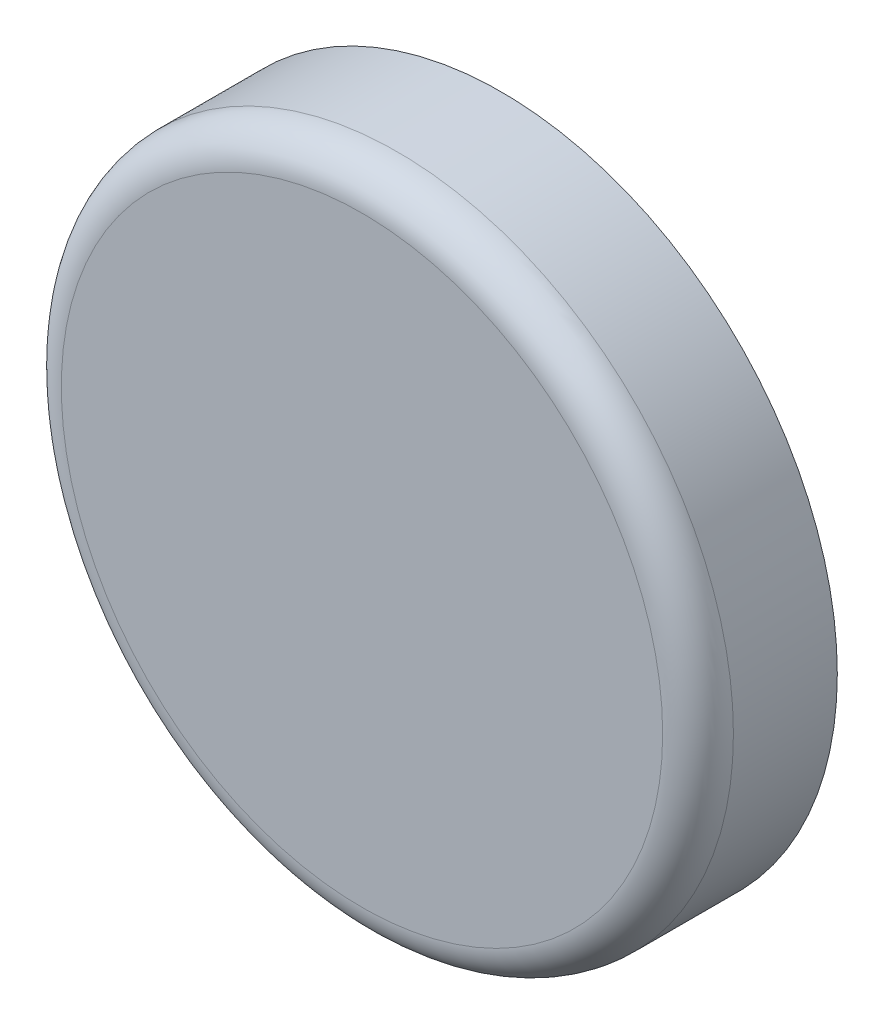
SolidWorks part; units mm, degrees
ref_plane "Front Plane" through (0, 0, 0) normal (0, 0, 1) x (1, 0, 0)
ref_plane "Top Plane" through (0, 0, 0) normal (0, 1, 0) x (1, 0, 0)
ref_plane "Right Plane" through (0, 0, 0) normal (1, 0, 0) x (0, 0, -1)
sketch "Sketch1" plane through (0, 0, 0) normal (0, 0, 1) x (1, 0, 0)
  circle A0 centre (0, 0) radius 12.065
  dimension "D1" = 24.13
extrude "Boss-Extrude1" add sketch "Sketch1" along normal blind 5
fillet "Fillet1" radius 1.27 1 edges at (12.065, 0, 5)
